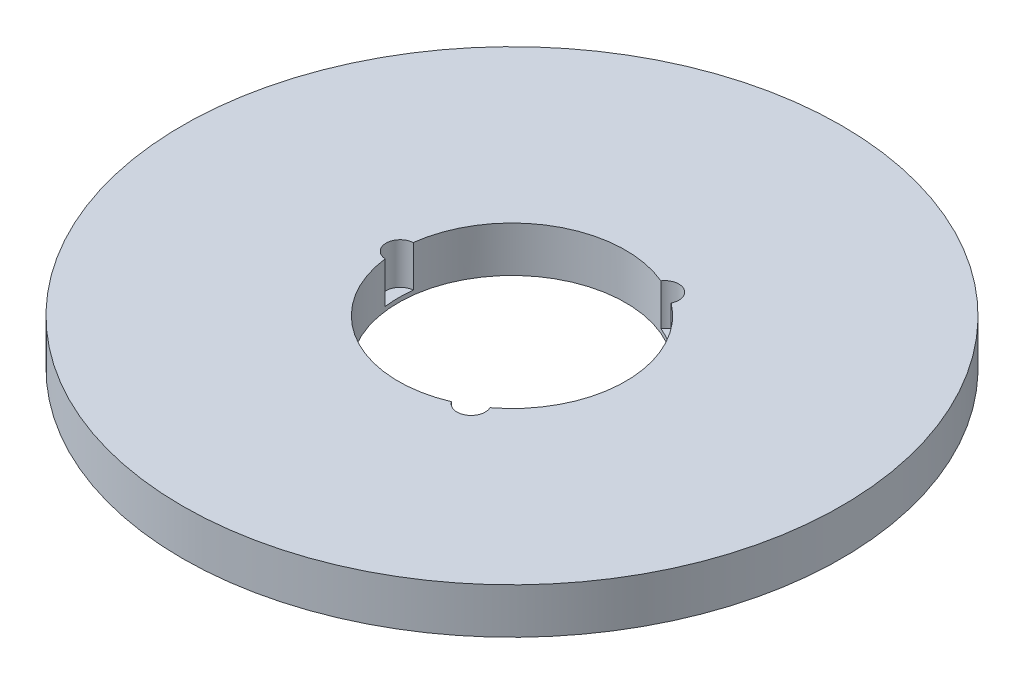
SolidWorks part; units mm, degrees
ref_plane "Front Plane" through (0, 0, 0) normal (0, 0, 1) x (1, 0, 0)
ref_plane "Top Plane" through (0, 0, 0) normal (0, 1, 0) x (1, 0, 0)
ref_plane "Right Plane" through (0, 0, 0) normal (1, 0, 0) x (0, 0, -1)
sketch "Sketch1" plane through (0, 0, 0) normal (0, 1, 0) x (1, 0, 0)
  circle A0 centre (0, 0) radius 72.5
  dimension "FLANGE_OD" = 145
extrude "Boss-Extrude1" add sketch "Sketch1" along normal blind 10
sketch "Sketch2" plane through (0, 0, 0) normal (0, 1, 0) x (1, 0, 0)
  circle A0 centre (0, 0) radius 25
  dimension "BORE_D" = 50
extrude "Cut-Extrude1" cut sketch "Sketch2" along normal through all
sketch "Sketch3" plane through (0, 10, 0) normal (0, 1, 0) x (1, 0, 0)
  circle A0 centre (0, 0) radius 24.5902 construction
  circle A1 centre (-24.5902, 0) radius 3.1074
  dimension "BOLT_D" = 6.2148
  dimension "BOLT_PCD" = 49.1805
extrude "Cut-Extrude2" cut sketch "Sketch3" against normal blind 9.0751
pattern_circular "CirPattern1" count 3 over 360 about axis through (0, 0, 0) along (0, 1, 0) of "Cut-Extrude2"
